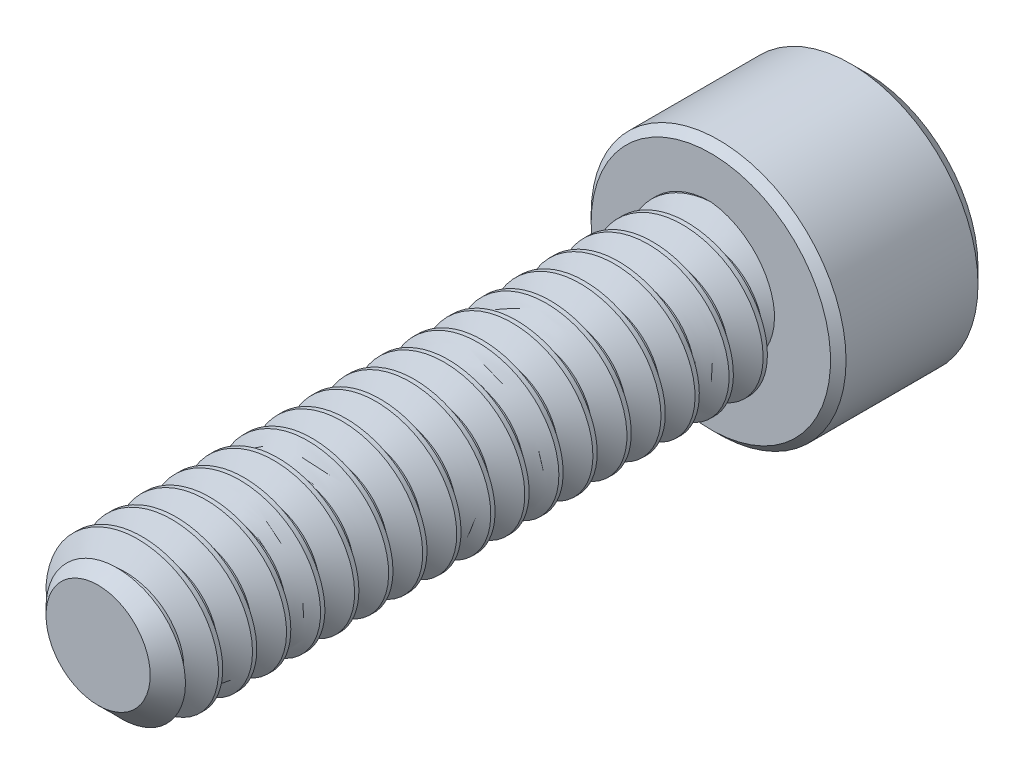
SolidWorks part; units mm, degrees
ref_plane "Front Plane" through (0, 0, 0) normal (0, 0, 1) x (1, 0, 0)
ref_plane "Top Plane" through (0, 0, 0) normal (0, 1, 0) x (1, 0, 0)
ref_plane "Right Plane" through (0, 0, 0) normal (1, 0, 0) x (0, 0, -1)
sketch "Sketch1" plane through (0, 0, 0) normal (0, 0, 1) x (1, 0, 0)
  line L0 (0, 2.413) -> (0, -2.413) construction
  circle A0 centre (0, 0) radius 2.413
  dimension "OD" = 4.826
extrude "Extrude1" add sketch "Sketch1" against normal blind 19.05
sketch "Sketch2" plane through (0, 0, 0) normal (0, 0, 1) x (1, 0, 0)
  circle A0 centre (0, 0) radius 2.413 construction
  circle A1 centre (0, 0) radius 2.413
curve "Helix/Spiral1" pitch 1.0583 height 20.1083 turns 19 parameters "pitch"=1.0583
chamfer "Chamfer3" distance 0.7937 angle 45 1 edges at (2.413, 0, 0)
sketch "Sketch3" plane through (0, 0, 0) normal (1, 0, 0) x (0, 0, -1)
  line L0 (-0.926, 2.413) -> (-0.5292, 1.7256)
  line L1 (-0.5292, 1.7256) -> (-0.3969, 1.7256)
  line L2 (-0.3969, 1.7256) -> (0, 2.413)
  line L3 (-0.926, 2.413) -> (0, 2.413)
  line L4 (-0.463, 2.413) -> (-0.463, 1.7256) construction
  line L5 (-0.7276, 2.0693) -> (-0.1984, 2.0693) construction
  line L6 (0, 2.413) -> (0, -2.413) construction
  dimension "D1" = 0.1323
  dimension "D2" = 0.5292
  dimension "D3" = 60
sweep "Cut-Sweep1" cut profiles "Sketch3" path "Helix/Spiral1"
sketch "Sketch6" plane through (0, 0, -19.05) normal (0, 0, -1) x (-1, 0, 0)
  circle A0 centre (0, 0) radius 3.9624
  dimension "head dia" = 7.9248
extrude "Extrude2" add sketch "Sketch6" along normal blind 4.826
sketch "Sketch7" plane through (0, 0, -23.876) normal (0, 0, -1) x (-1, 0, 0)
  line L1 (0, 2.2914) -> (-1.9844, 1.1457)
  line L2 (-1.9844, 1.1457) -> (-1.9844, -1.1457)
  line L3 (-1.9844, -1.1457) -> (0, -2.2914)
  line L4 (0, -2.2914) -> (1.9844, -1.1457)
  line L5 (1.9844, -1.1457) -> (1.9844, 1.1457)
  line L6 (1.9844, 1.1457) -> (0, 2.2914)
  circle A0 centre (0, 0) radius 1.9844 construction
  dimension "hex dia" = 3.9688
extrude "Cut-Extrude1" cut sketch "Sketch7" against normal blind 2.9766
sketch "Sketch8" plane through (0, 0, -23.876) normal (0, 0, -1) x (-1, 0, 0)
  circle A0 centre (0, 0) radius 2.2914
extrude "Cut-Extrude2" cut sketch "Sketch8" against normal blind 0.4826 draft 45
chamfer "Chamfer1" distance 0.4826 angle 45 1 edges at (-3.9624, 0, -23.876)
chamfer "Chamfer2" distance 0.2413 angle 45 1 edges at (-3.9624, 0, -19.05)
sketch "Sketch9" plane through (0, 0, 0) normal (1, 0, 0) x (0, 0, -1)
  line L0 (0, 2.413) -> (0, -2.413) construction
  line L1 (5.8208, 2.413) -> (5.8208, -2.413) construction
  line L2 (19.05, 3.9624) -> (19.05, -3.9624) construction
  line L3 (23.876, 3.9624) -> (23.876, -3.9624) construction
  line L4 (23.876, 0) -> (0, 0) construction
  dimension "D1" = 5.8208
  dimension "D2" = 4.826
  dimension "D3" = 7.9248
  dimension "D4" = 0.635
  dimension "D5" = 0.3302
equation "\"D3@Helix/Spiral1\" = \"screw length@Extrude1\"+\"pitch@Helix/Spiral1\""
equation "\"D1@Sketch3\" = \"pitch@Helix/Spiral1\"*.125"
equation "\"D2@Sketch3\" = \"pitch@Helix/Spiral1\"*.5"
equation "\"D1@Cut-Extrude1\" = \"hex dia@Sketch7\"*.75"
equation "\"D1@Chamfer1\" = \"head depth@Extrude2\"/10"
equation "\"D1@Sketch9\" = \"pitch@Helix/Spiral1\"*5.5"
equation "\"D1@Chamfer2\" = \"D1@Chamfer1\"/2"
equation "\"D1@Cut-Extrude2\" = \"D1@Chamfer2\"*2"
equation "\"D1@Chamfer3\" = \"pitch@Helix/Spiral1\"*.750"
equation "\"D2@Sketch9\" = \"head depth@Extrude2\""
equation "\"D3@Sketch9\" = \"head dia@Sketch6\""
equation "\"D4@Sketch9\" = \"screw length@Extrude1\""
